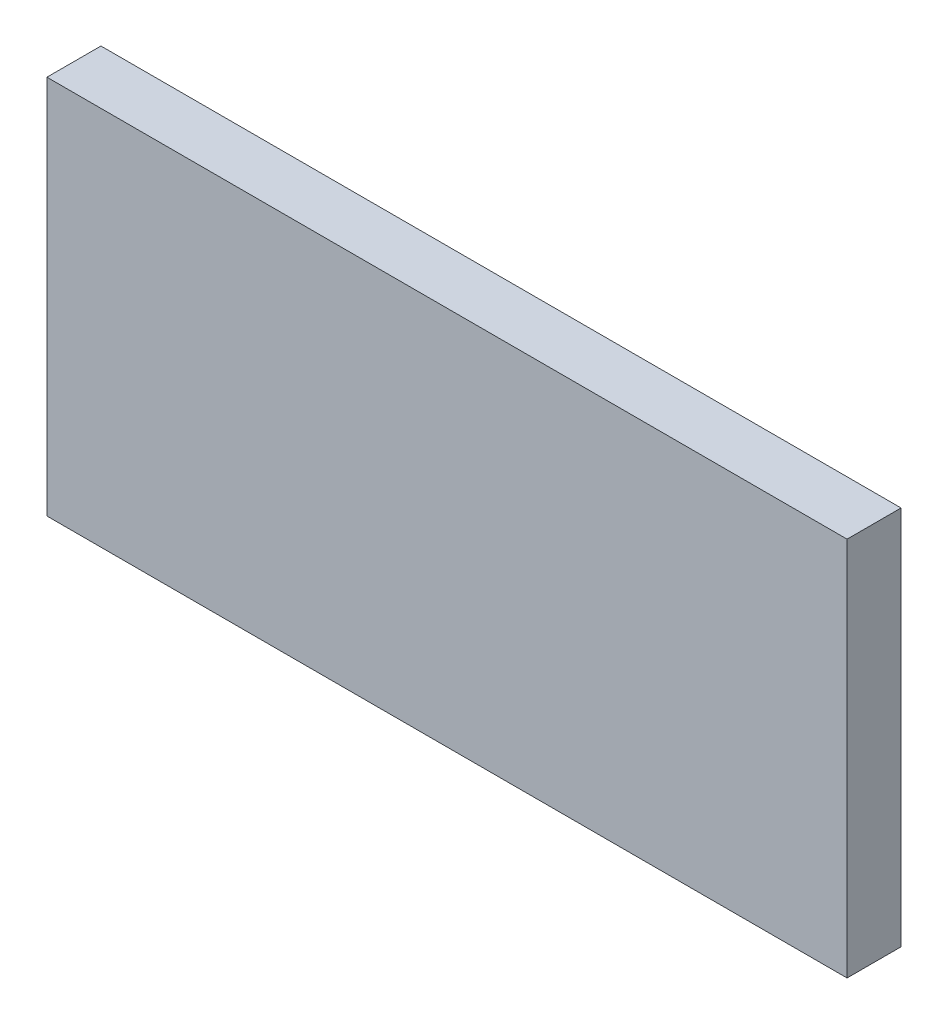
SolidWorks part; units mm, degrees
ref_plane "Plan de face" through (0, 0, 0) normal (0, 0, 1) x (1, 0, 0)
ref_plane "Plan de dessus" through (0, 0, 0) normal (0, 1, 0) x (1, 0, 0)
ref_plane "Plan de droite" through (0, 0, 0) normal (1, 0, 0) x (0, 0, -1)
sketch "Esquisse1" plane through (0, 0, 0) normal (0, 0, 1) x (1, 0, 0)
  line L1 (0, 0) -> (400, 0)
  line L2 (0, 0) -> (0, 190)
  line L3 (0, 190) -> (400, 190)
  line L4 (400, 0) -> (400, 190)
  dimension "D1" = 190
  dimension "D2" = 400
extrude "Boss.-Extru.1" add sketch "Esquisse1" along normal blind 27
